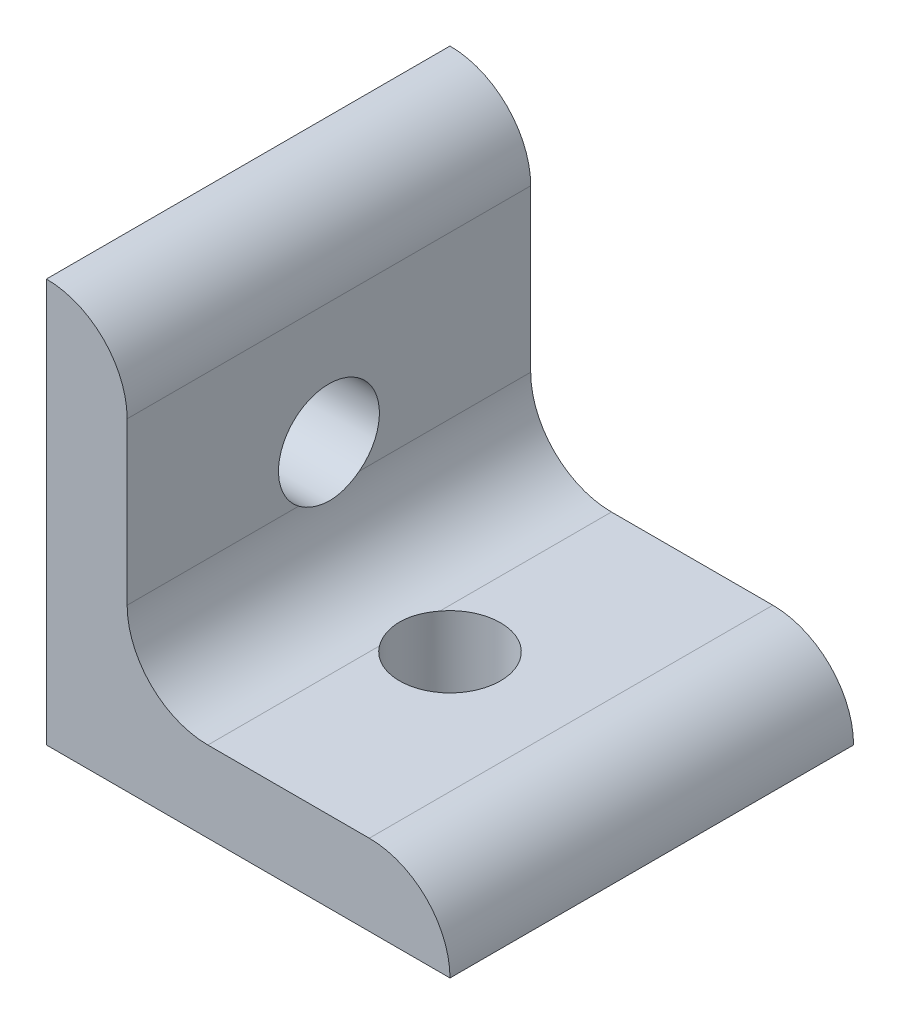
SolidWorks part; units mm, degrees
ref_plane "Front" through (0, 0, 0) normal (0, 0, 1) x (1, 0, 0)
ref_plane "Top" through (0, 0, 0) normal (0, 1, 0) x (1, 0, 0)
ref_plane "Right" through (0, 0, 0) normal (1, 0, 0) x (0, 0, -1)
sketch "Sketch1" plane through (0, 0, 0) normal (0, 0, 1) x (1, 0, 0)
  line L0 (0, 0) -> (0, -25.4)
  line L1 (0, -25.4) -> (25.4, -25.4)
  line L2 (25.4, -25.4) -> (25.4, -20.32)
  line L3 (25.4, -20.32) -> (5.08, -20.32)
  line L4 (5.08, -20.32) -> (5.08, 0)
  line L5 (5.08, 0) -> (0, 0)
extrude "Boss-Extrude1" add sketch "Sketch1" along normal blind 25.4
fillet "Fillet1" radius 5.08 3 edges at (5.08, -20.32, 12.7) (5.08, 0, 12.7) (25.4, -20.32, 12.7)
sketch "Sketch2" plane through (0, -25.4, 0) normal (0, -1, 0) x (1, 0, 0)
  line L0 (0, 25.4) -> (25.4, 0)
  circle A0 centre (12.7, 12.7) radius 3.175
extrude "Cut-Extrude1" cut sketch "Sketch2" against normal blind 25.4 contours L0 A0 | L0 A0 region at (13.6528, -25.4, 13.6528) region at (11.7472, -25.4, 11.7472)
sketch "Sketch3" plane through (0, 0, 0) normal (-1, 0, 0) x (0, 0, 1)
  line L0 (25.4, -25.4) -> (0, 0)
  circle A0 centre (12.7, -12.7) radius 3.175
extrude "Cut-Extrude2" cut sketch "Sketch3" against normal blind 25.4 contours L0 A0 | L0 A0 region at (0, -13.6528, 11.7472) region at (0, -11.7472, 13.6528)
